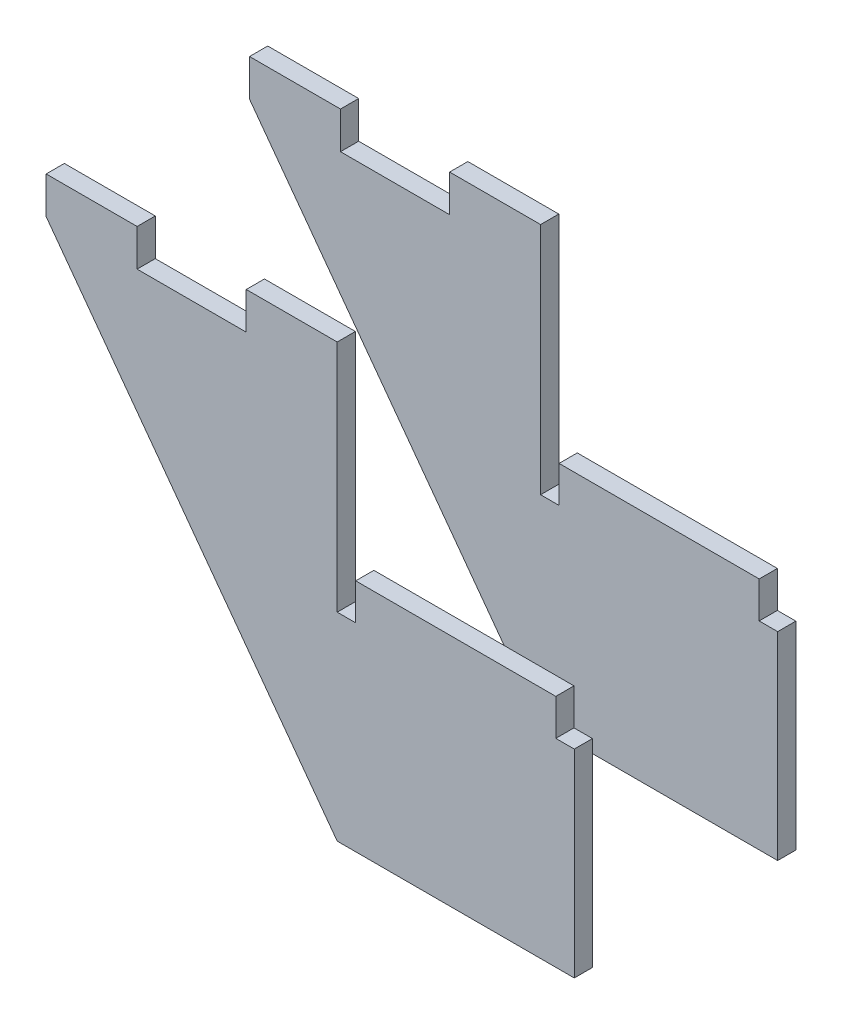
SolidWorks part; units mm, degrees
note: The reader was unsure of these and kept them because the rebuilt part matched: shared geometry of "Sketch1<2>".
material "Gillfab4009"
ref_plane "Front Plane" through (0, 0, 0) normal (0, 0, 1) x (1, 0, 0)
ref_plane "Top Plane" through (0, 0, 0) normal (0, 1, 0) x (1, 0, 0)
ref_plane "Right Plane" through (0, 0, 0) normal (1, 0, 0) x (0, 0, -1)
sketch "Sketch1" plane through (0, 0, 0) normal (0, 0, 1) x (1, 0, 0)
  line L0 (-210.16, -2161.2189) -> (-200, -2161.2189)
  line L1 (-79.84, -2161.2189) -> (-79.84, -2270.2189)
  line L2 (-79.84, -2270.2189) -> (-210.16, -2270.2189)
  line L3 (-210.16, -2270.2189) -> (-370.16, -2052.9116)
  line L4 (-332.7218, -2052.9116) -> (-408.9218, -2052.9116) construction
  line L5 (-320.16, -2052.9116) -> (-260.16, -2052.9116)
  line L6 (-134.539, -2052.9116) -> (-332.7218, -2052.9116) construction
  line L7 (-210.16, -2052.9116) -> (-210.16, -2161.2189)
  line L8 (-200, -2161.2189) -> (-200, -2141.2189)
  line L9 (-200, -2052.9116) -> (-200, -2161.2189) construction
  line L10 (-200, -2141.2189) -> (-90, -2141.2189)
  line L11 (-90, -2052.9116) -> (-90, -2161.2189) construction
  line L12 (-90, -2141.2189) -> (-90, -2161.2189)
  line L13 (-90, -2161.2189) -> (-79.84, -2161.2189)
  line L14 (-370.16, -2052.9116) -> (-370.16, -2032.5916)
  line L15 (-370.16, -2032.5916) -> (-320.16, -2032.5916)
  line L16 (-320.16, -2032.5916) -> (-320.16, -2052.9116)
  line L17 (-210.16, -2052.9116) -> (-210.16, -2032.5916)
  line L18 (-210.16, -2032.5916) -> (-260.16, -2032.5916)
  line L19 (-260.16, -2032.5916) -> (-260.16, -2052.9116)
  line L20 (-260.16, -2032.5916) -> (-320.16, -2032.5916) construction
  line L21 (-90, -2161.2189) -> (-200, -2161.2189) construction
  dimension "D1" = 110
  dimension "D2" = 20
  dimension "D3" = 50
  dimension "D4" = 160
extrude "Boss-Extrude1" add sketch "Sketch1" along normal blind 10 from surface at 236.8927
extrude "Boss-Extrude2" add sketch "Sketch1<2>" against normal blind 10 from surface separate body
sketch "Sketch1<2>" plane through (0, 0, 0) normal (0, 0, 1) x (1, 0, 0) same geometry as "Sketch1"
